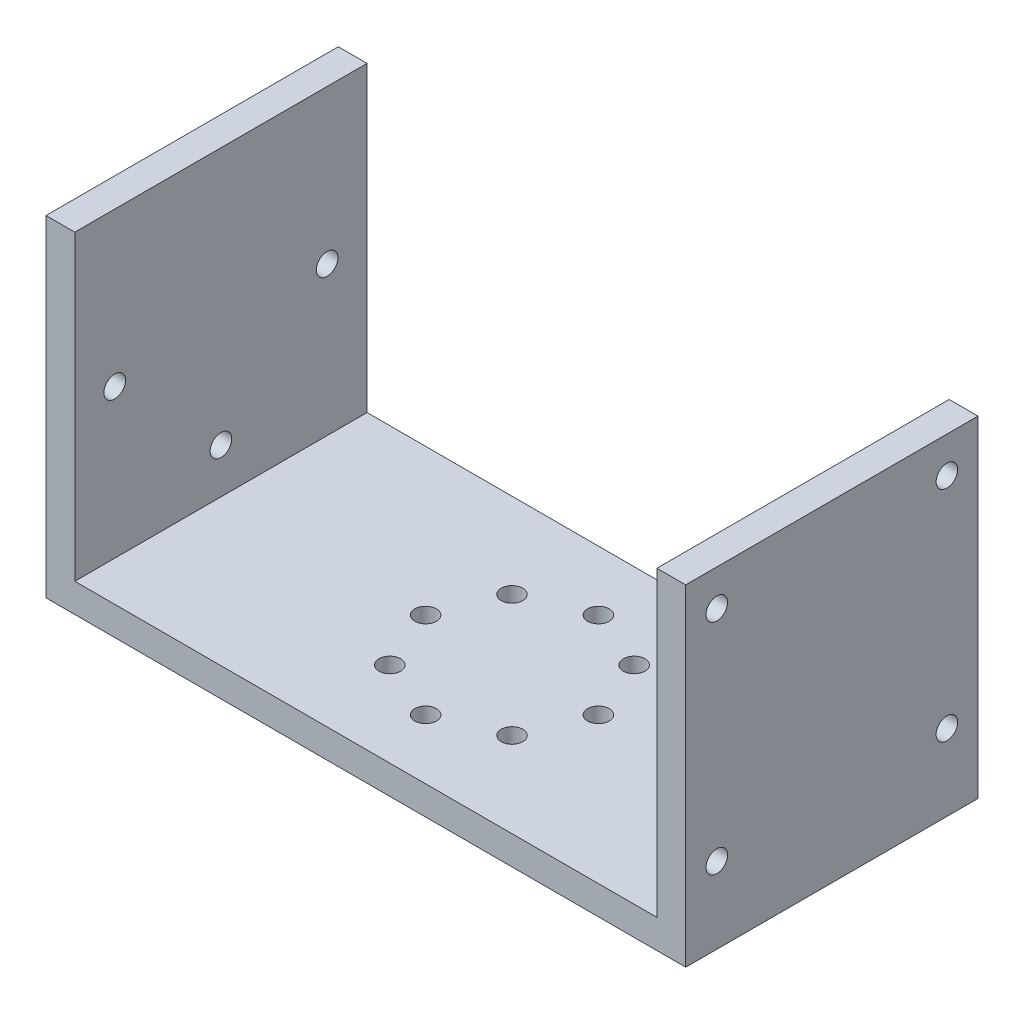
SolidWorks part; units mm, degrees
ref_plane "Front Plane" through (0, 0, 0) normal (0, 0, 1) x (1, 0, 0)
ref_plane "Top Plane" through (0, 0, 0) normal (0, 1, 0) x (1, 0, 0)
ref_plane "Right Plane" through (0, 0, 0) normal (1, 0, 0) x (0, 0, -1)
sketch "Sketch1" plane through (0, 0, 0) normal (0, 1, 0) x (1, 0, 0)
  line L1 (0, 0) -> (44.43, 0)
  line L2 (0, 0) -> (0, 20.3)
  line L3 (0, 20.3) -> (44.43, 20.3)
  line L4 (44.43, 0) -> (44.43, 20.3)
  dimension "D1" = 44.43
  dimension "D2" = 20.3
extrude "YawMount" add sketch "Sketch1" along normal blind 2
sketch "Sketch2" plane through (0, 2, 0) normal (0, 1, 0) x (1, 0, 0)
  line L0 (0, 0) -> (44.43, 0) construction
  line L1 (0, 20.3) -> (2, 20.3)
  line L2 (0, 20.3) -> (0, 0)
  line L3 (0, 0) -> (2, 0)
  line L4 (2, 20.3) -> (2, 0)
  line L6 (44.43, 20.3) -> (42.43, 20.3)
  line L7 (44.43, 20.3) -> (44.43, 0)
  line L8 (44.43, 0) -> (42.43, 0)
  line L9 (42.43, 20.3) -> (42.43, 0)
  dimension "D1" = 2
  dimension "D2" = 2
extrude "BodyConnectors" add sketch "Sketch2" along normal blind 21
sketch "Sketch3" plane through (0, 0, 0) normal (0, -1, 0) x (1, 0, 0)
  line L0 (0, -20.3) -> (0, 0) construction
  line L1 (44.43, -20.3) -> (0, -20.3) construction
  circle A0 centre (22.215, -10.15) radius 4
  point P4 (0, -10.15)
  point P7 (22.215, -20.3)
  dimension "D1" = 8
extrude "Axle-Counterbore" cut sketch "Sketch3" against normal blind 1.5
sketch "Sketch5" plane through (0, 0, 0) normal (0, -1, 0) x (1, 0, 0)
  line L0 (0, -20.3) -> (0, 0) construction
  line L1 (44.43, -20.3) -> (0, -20.3) construction
  circle A0 centre (16.215, -10.15) radius 0.75
  circle A3 centre (22.215, -10.15) radius 4 construction
  circle A4 centre (17.9724, -5.9074) radius 0.75
  circle A5 centre (22.215, -4.15) radius 0.75
  circle A6 centre (26.4576, -5.9074) radius 0.75
  circle A7 centre (28.215, -10.15) radius 0.75
  circle A8 centre (26.4576, -14.3926) radius 0.75
  circle A9 centre (22.215, -16.15) radius 0.75
  circle A10 centre (17.9724, -14.3926) radius 0.75
  point P6 (0, -10.15)
  point P24 (22.215, -10.15)
  point P25 (22.215, -20.3)
  dimension "D1" = 1.5
  dimension "D2" = 6
  dimension "D3" = 8
extrude "azel-mountscrews" cut sketch "Sketch5" against normal up to surface (2 mm away) up to face at (22.215, 2, -10.15)
sketch "Sketch6" plane through (2, 0, 0) normal (1, 0, 0) x (0, 0, -1)
  line L0 (0, 23) -> (20.3, 23) construction
  line L3 (0, 2) -> (20.3, 2) construction
  circle A1 centre (10.15, 5.12) radius 0.75
  circle A2 centre (17.525, 12.33) radius 0.75
  circle A3 centre (2.775, 12.33) radius 0.75
  point P5 (10.15, 23)
  dimension "D2" = 1.5
  dimension "D3" = 14.75
  dimension "D4" = 7.21
  dimension "D5" = 7.375
  dimension "D1" = 3.12
extrude "GearSide-Screws" cut sketch "Sketch6" against normal up to surface (2 mm away) up to face at (0, 11.5, -10.15)
sketch "Sketch7" plane through (42.43, 0, 0) normal (-1, 0, 0) x (0, 0, 1)
  line L0 (-20.3, 2) -> (0, 2) construction
  circle A0 centre (-2.16, 5.3) radius 0.75
  circle A1 centre (-18.14, 5.3) radius 0.75
  circle A2 centre (-18.14, 20.5) radius 0.75
  circle A3 centre (-2.16, 20.5) radius 0.75
  point P14 (-10.15, 2)
  dimension "D2" = 1.5
  dimension "D1" = 3.3
  dimension "D3" = 15.98
  dimension "D4" = 7.99
  dimension "D5" = 15.2
extrude "SmoothSide-Screws" cut sketch "Sketch7" against normal up to surface (2 mm away) up to face at (44.43, 11.5, -10.15)
equation "\"srv_w\"= 40.43mm'width of Sain Smart SR319"
equation "\"D1@Sketch1\"=\"srv_w\" + \"mnt_thick\"*2"
equation "\"srv_h\"= 40.61mm'height of Sain Smart SR319"
equation "\"srv_d\"= 20.3mm'depth of Sain Smart SR319"
equation "\"D2@Sketch1\"=\"srv_d\""
equation "\"mnt_thick\"= 2mm'thickness of bracket"
equation "\"D1@YawMount\" = \"mnt_thick\""
equation "\"D2@Sketch2\"=\"mnt_thick\""
equation "\"D1@Sketch2\"=\"mnt_thick\""
equation "\"D5@Sketch6\"=\"D3@Sketch6\"/2"
equation "\"D4@Sketch7\"=\"D3@Sketch7\"/2"
equation "\"clearance\"= 1mm'extra space between bracket and roll rotator servo"
equation "\"D1@Sketch6\"=\"clearance\"+2.12mm"
equation "\"D1@Sketch7\"=\"clearance\"+2.3mm"
